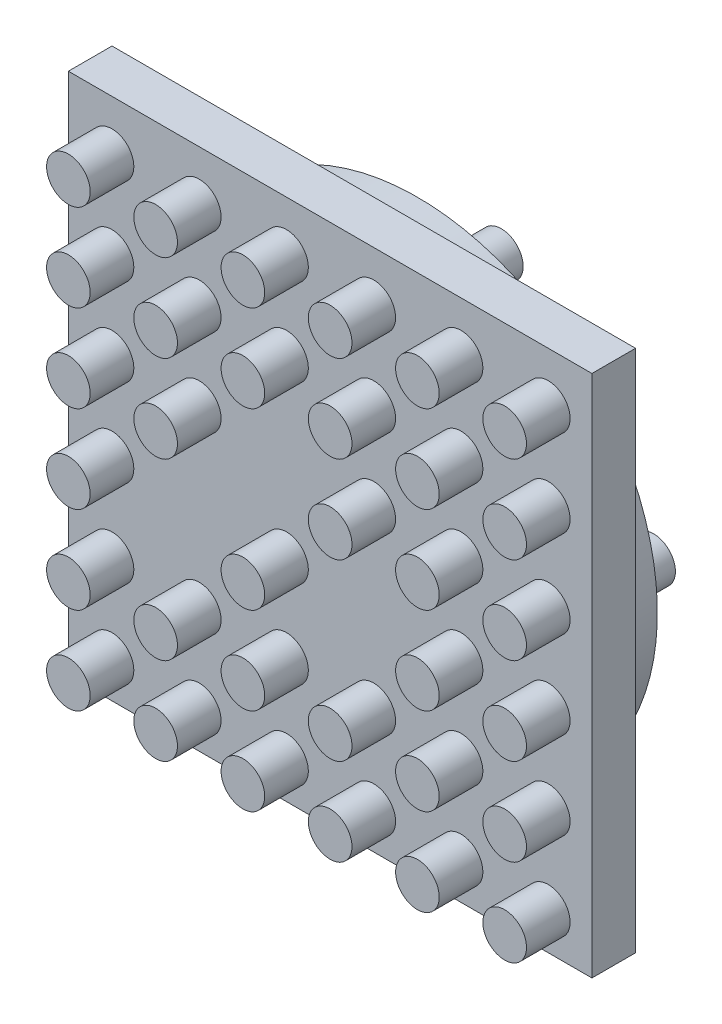
SolidWorks part; units mm, degrees
note: The reader was unsure of these and kept them because the rebuilt part matched: shared geometry of "Sketch1<3>", "Sketch3<3>".
ref_plane "정면" through (0, 0, 0) normal (0, 0, 1) x (1, 0, 0)
ref_plane "윗면" through (0, 0, 0) normal (0, 1, 0) x (1, 0, 0)
ref_plane "우측면" through (0, 0, 0) normal (1, 0, 0) x (0, 0, -1)
sketch "Sketch1" plane through (0, 0, 0) normal (0, 0, 1) x (1, 0, 0)
  line L1 (-60, 120) -> (60, 120)
  line L2 (-60, 120) -> (-60, 0)
  line L3 (-60, 0) -> (60, 0)
  line L4 (60, 120) -> (60, 0)
  circle A0 centre (-50, 108.5552) radius 5
  point P4 (0, 0)
  dimension "D5" = 10
  dimension "D1" = 120
  dimension "D2" = 120
  dimension "D3" = 11.4448
  dimension "D4" = 10
extrude "Boss-Extrude1" add sketch "Sketch1" against normal blind 10 contours A0 | L4 L1 L2 L3 A0
extrude "Boss-Extrude2" add sketch "Sketch1<3>" along normal blind 10 contours A0
sketch "Sketch1<3>" plane through (0, 0, 0) normal (0, 0, 1) x (1, 0, 0) same geometry as "Sketch1"
pattern_linear "LPattern2" count 6 spacing 20 along (1, 0, 0) count 9 spacing 20 along (0, -1, 0) of "Boss-Extrude2"
sketch "Sketch3" plane through (0, 0, -10) normal (0, 0, -1) x (-1, 0, 0)
  line L1 (60, 0) -> (-60, 0) construction
  circle A0 centre (0, 60) radius 55
  circle A1 centre (0, 60) radius 5
  circle A2 centre (20.9185, 97.737) radius 5
  dimension "D2" = 110
  dimension "D3" = 10
  dimension "D4" = 10
  dimension "D1" = 60
extrude "Boss-Extrude3" add sketch "Sketch3" along normal blind 10 contours A1 | A2 | A0 A2 A1
extrude "Boss-Extrude4" add sketch "Sketch3<3>" along a picked direction on the side of the normal blind 21 separate body contours A2 | A1
sketch "Sketch3<3>" plane through (0, 0, -10) normal (0, 0, -1) x (-1, 0, 0) same geometry as "Sketch3"
pattern_circular "CirPattern1" count 9 every 40 about axis through (0, 60, 0) along (0, 0, 1) of "Boss-Extrude4"
